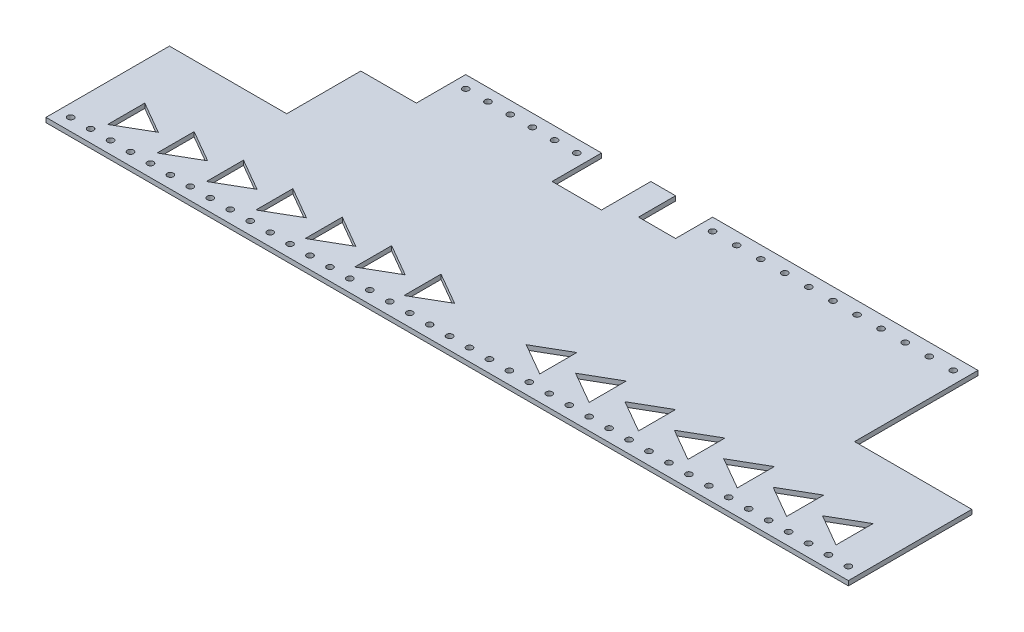
SolidWorks part; units mm, degrees
note: The reader was unsure of these and kept them because the rebuilt part matched: thickness of "Base-Flange1", "Sheet-Metal1", "Sheet-Metal2", "Sheet-Metal3", "Sheet-Metal4", "Sheet-Metal5", "Sheet-Metal6", "Sheet-Metal7".
material "6061 Alloy"
ref_plane "Front Plane" through (0, 0, 0) normal (0, 0, 1) x (1, 0, 0)
ref_plane "Top Plane" through (0, 0, 0) normal (0, 1, 0) x (1, 0, 0)
ref_plane "Right Plane" through (0, 0, 0) normal (1, 0, 0) x (0, 0, -1)
sketch "Sketch1" plane through (0, 0, 0) normal (0, 1, 0) x (1, 0, 0)
  line L1 (412.75, 127) -> (-412.75, 127)
  line L2 (412.75, 127) -> (412.75, -127)
  line L3 (412.75, -127) -> (-412.75, -127)
  line L4 (-412.75, 127) -> (-412.75, -127)
  line L5 (412.75, 127) -> (-412.75, -127) construction
  line L6 (412.75, -127) -> (-412.75, 127) construction
  point P0 (0, 0)
  dimension "D1" = 254
  dimension "D2" = 825.5
base flange "Base-Flange1" sketch "Sketch1" thickness 4.7625 reverse thickness direction no parameters "D1"=3.175
sketch "Sketch6" plane through (0, 0, 0) normal (0, 1, 0) x (1, 0, 0)
  line L0 (412.75, 127) -> (-412.75, 127) construction
  line L1 (-19.05, 165.1) -> (19.05, 165.1)
  line L2 (-19.05, 165.1) -> (-19.05, 88.9)
  line L3 (-19.05, 88.9) -> (19.05, 88.9)
  line L4 (19.05, 165.1) -> (19.05, 88.9)
  line L5 (-19.05, 165.1) -> (19.05, 88.9) construction
  line L6 (-19.05, 88.9) -> (19.05, 165.1) construction
  line L7 (-412.75, 127) -> (-412.75, -127) construction
  line L8 (-533.4, 101.6) -> (-292.1, 101.6)
  line L9 (-533.4, 101.6) -> (-533.4, 0)
  line L10 (-533.4, 0) -> (-292.1, 0)
  line L11 (-292.1, 101.6) -> (-292.1, 0)
  line L12 (-533.4, 101.6) -> (-292.1, 0) construction
  line L13 (-533.4, 0) -> (-292.1, 101.6) construction
  line L14 (412.75, -127) -> (412.75, 127) construction
  line L15 (533.4, 0) -> (292.1, 0)
  line L16 (533.4, 0) -> (533.4, 101.6)
  line L17 (533.4, 101.6) -> (292.1, 101.6)
  line L18 (292.1, 0) -> (292.1, 101.6)
  line L19 (533.4, 0) -> (292.1, 101.6) construction
  line L20 (533.4, 101.6) -> (292.1, 0) construction
  line L22 (-44.45, 76.2) -> (-95.25, 76.2)
  line L23 (-44.45, 76.2) -> (-44.45, 177.8)
  line L24 (-44.45, 177.8) -> (-95.25, 177.8)
  line L25 (-95.25, 76.2) -> (-95.25, 177.8)
  line L26 (-44.45, 76.2) -> (-95.25, 177.8) construction
  line L27 (-44.45, 177.8) -> (-95.25, 76.2) construction
  point P0 (0, 127)
  point P7 (-412.75, 50.8)
  point P14 (412.75, 50.8)
  point P21 (-69.85, 127)
  dimension "D1" = 38.1
  dimension "D2" = 76.2
  dimension "D3" = 241.3
  dimension "D4" = 101.6
  dimension "D5" = 25.4
  dimension "D6" = 241.3
  dimension "D7" = 101.6
  dimension "D8" = 25.4
  dimension "D9" = 50.8
  dimension "D10" = 101.6
  dimension "D11" = 25.4
extrude "Cut-Extrude1" cut sketch "Sketch6" against normal through all normal cut yes
sketch "Sketch7" plane through (0, 0, 0) normal (0, 1, 0) x (1, 0, 0)
  line L1 (-412.75, 127) -> (-234.95, 127)
  line L2 (-412.75, 127) -> (-412.75, 76.2)
  line L3 (-412.75, 76.2) -> (-234.95, 76.2)
  line L4 (-234.95, 127) -> (-234.95, 76.2)
  line L5 (412.75, 127) -> (292.1, 127)
  line L6 (412.75, 127) -> (412.75, 101.6)
  line L7 (412.75, 101.6) -> (292.1, 101.6)
  line L8 (292.1, 127) -> (292.1, 101.6)
  dimension "D1" = 50.8
  dimension "D2" = 177.8
extrude "Cut-Extrude2" cut sketch "Sketch7" against normal through all normal cut yes
sketch "Sketch8" plane through (0, 0, 0) normal (0, 1, 0) x (1, 0, 0)
  line L0 (412.75, -127) -> (412.75, 0) construction
  line L1 (341.6544, -82.55) -> (374.65, -101.6)
  line L2 (374.65, -101.6) -> (374.65, -63.5)
  line L3 (374.65, -63.5) -> (341.6544, -82.55)
  line L4 (323.85, -101.6) -> (323.85, -63.5)
  line L5 (323.85, -63.5) -> (290.8544, -82.55)
  line L6 (290.8544, -82.55) -> (323.85, -101.6)
  line L7 (273.05, -101.6) -> (273.05, -63.5)
  line L8 (273.05, -63.5) -> (240.0544, -82.55)
  line L9 (240.0544, -82.55) -> (273.05, -101.6)
  line L10 (222.25, -101.6) -> (222.25, -63.5)
  line L11 (222.25, -63.5) -> (189.2544, -82.55)
  line L12 (189.2544, -82.55) -> (222.25, -101.6)
  line L13 (171.45, -101.6) -> (171.45, -63.5)
  line L14 (171.45, -63.5) -> (138.4544, -82.55)
  line L15 (138.4544, -82.55) -> (171.45, -101.6)
  line L16 (120.65, -101.6) -> (120.65, -63.5)
  line L17 (120.65, -63.5) -> (87.6544, -82.55)
  line L18 (87.6544, -82.55) -> (120.65, -101.6)
  line L19 (69.85, -101.6) -> (69.85, -63.5)
  line L20 (69.85, -63.5) -> (36.8544, -82.55)
  line L21 (36.8544, -82.55) -> (69.85, -101.6)
  line L22 (0, 0) -> (0, -95.9685) construction
  line L23 (-36.8544, -82.55) -> (-69.85, -101.6)
  line L24 (-69.85, -63.5) -> (-36.8544, -82.55)
  line L25 (-69.85, -101.6) -> (-69.85, -63.5)
  line L26 (-87.6544, -82.55) -> (-120.65, -101.6)
  line L27 (-120.65, -63.5) -> (-87.6544, -82.55)
  line L28 (-120.65, -101.6) -> (-120.65, -63.5)
  line L29 (-138.4544, -82.55) -> (-171.45, -101.6)
  line L30 (-171.45, -63.5) -> (-138.4544, -82.55)
  line L31 (-171.45, -101.6) -> (-171.45, -63.5)
  line L32 (-189.2544, -82.55) -> (-222.25, -101.6)
  line L33 (-222.25, -63.5) -> (-189.2544, -82.55)
  line L34 (-222.25, -101.6) -> (-222.25, -63.5)
  line L35 (-240.0544, -82.55) -> (-273.05, -101.6)
  line L36 (-273.05, -63.5) -> (-240.0544, -82.55)
  line L37 (-273.05, -101.6) -> (-273.05, -63.5)
  line L38 (-290.8544, -82.55) -> (-323.85, -101.6)
  line L39 (-323.85, -63.5) -> (-290.8544, -82.55)
  line L40 (-323.85, -101.6) -> (-323.85, -63.5)
  line L41 (-374.65, -63.5) -> (-341.6544, -82.55)
  line L42 (-374.65, -101.6) -> (-374.65, -63.5)
  line L43 (-341.6544, -82.55) -> (-374.65, -101.6)
  line L46 (-412.75, -127) -> (412.75, -127) construction
  line L47 (19.05, -101.6) -> (19.05, -63.5) [skipped]
  line L48 (-13.9456, -82.55) -> (19.05, -101.6) [skipped]
  line L49 (19.05, -63.5) -> (-13.9456, -82.55) [skipped]
  line L50 (-31.75, -63.5) -> (-64.7456, -82.55) [skipped]
  line L51 (-31.75, -101.6) -> (-31.75, -63.5) [skipped]
  line L52 (-64.7456, -82.55) -> (-31.75, -101.6) [skipped]
  line L53 (-82.55, -101.6) -> (-82.55, -63.5) [skipped]
  line L54 (-82.55, -63.5) -> (-115.5456, -82.55) [skipped]
  line L55 (-115.5456, -82.55) -> (-82.55, -101.6) [skipped]
  line L56 (-133.35, -101.6) -> (-133.35, -63.5) [skipped]
  line L57 (-133.35, -63.5) -> (-166.3456, -82.55) [skipped]
  line L58 (-166.3456, -82.55) -> (-133.35, -101.6) [skipped]
  line L59 (-184.15, -101.6) -> (-184.15, -63.5) [skipped]
  line L60 (-184.15, -63.5) -> (-217.1456, -82.55) [skipped]
  line L61 (-217.1456, -82.55) -> (-184.15, -101.6) [skipped]
  line L62 (-234.95, -101.6) -> (-234.95, -63.5) [skipped]
  line L63 (-234.95, -63.5) -> (-267.9456, -82.55) [skipped]
  line L64 (-267.9456, -82.55) -> (-234.95, -101.6) [skipped]
  line L65 (-285.75, -101.6) -> (-285.75, -63.5) [skipped]
  line L66 (-285.75, -63.5) -> (-318.7456, -82.55) [skipped]
  line L67 (-318.7456, -82.55) -> (-285.75, -101.6) [skipped]
  line L68 (-336.55, -101.6) -> (-336.55, -63.5) [skipped]
  line L69 (-336.55, -63.5) -> (-369.5456, -82.55) [skipped]
  line L70 (-369.5456, -82.55) -> (-336.55, -101.6) [skipped]
  circle A0 centre (363.6515, -82.55) radius 10.9985 construction
  circle A1 centre (-363.6515, -82.55) radius 10.9985 construction
  dimension "D1" = 38.1
  dimension "D2" = 38.1
  dimension "D4" = 25.4
  dimension "D3" = 15
extrude "Cut-Extrude3" cut sketch "Sketch8" against normal through all normal cut yes
sketch "Sketch9" plane through (0, 0, 0) normal (0, 1, 0) x (1, 0, 0)
  line L0 (292.1, 127) -> (292.1, 0) construction
  line L1 (292.1, 127) -> (19.05, 127) construction
  line L2 (19.05, 88.9) -> (19.05, 127) construction
  circle A0 centre (279.4, 114.3) radius 3.175
  circle A1 centre (254.635, 114.3) radius 3.175
  circle A2 centre (229.87, 114.3) radius 3.175
  circle A3 centre (205.105, 114.3) radius 3.175
  circle A4 centre (180.34, 114.3) radius 3.175
  circle A5 centre (155.575, 114.3) radius 3.175
  circle A6 centre (130.81, 114.3) radius 3.175
  circle A7 centre (106.045, 114.3) radius 3.175
  circle A8 centre (81.28, 114.3) radius 3.175
  circle A9 centre (56.515, 114.3) radius 3.175
  circle A10 centre (31.75, 114.3) radius 3.175
  dimension "D1" = 6.35
  dimension "D2" = 12.7
  dimension "D3" = 12.7
  dimension "D5" = 12.7
  dimension "D4" = 11
extrude "Cut-Extrude4" cut sketch "Sketch9" against normal blind 7.62 normal cut yes
sketch "Sketch10" plane through (0, 0, 0) normal (0, 1, 0) x (1, 0, 0)
  line L0 (412.75, -127) -> (412.75, 0) construction
  line L1 (-412.75, -127) -> (412.75, -127) construction
  line L2 (-412.75, 0) -> (-412.75, -127) construction
  circle A0 centre (400.05, -114.3) radius 3.175
  circle A1 centre (379.5346, -114.3) radius 3.175
  circle A2 centre (359.0192, -114.3) radius 3.175
  circle A3 centre (338.5038, -114.3) radius 3.175
  circle A4 centre (317.9885, -114.3) radius 3.175
  circle A5 centre (297.4731, -114.3) radius 3.175
  circle A6 centre (276.9577, -114.3) radius 3.175
  circle A7 centre (256.4423, -114.3) radius 3.175
  circle A8 centre (235.9269, -114.3) radius 3.175
  circle A9 centre (215.4115, -114.3) radius 3.175
  circle A10 centre (194.8962, -114.3) radius 3.175
  circle A11 centre (174.3808, -114.3) radius 3.175
  circle A12 centre (153.8654, -114.3) radius 3.175
  circle A13 centre (133.35, -114.3) radius 3.175
  circle A14 centre (112.8346, -114.3) radius 3.175
  circle A15 centre (92.3192, -114.3) radius 3.175
  circle A16 centre (71.8038, -114.3) radius 3.175
  circle A17 centre (51.2885, -114.3) radius 3.175
  circle A18 centre (30.7731, -114.3) radius 3.175
  circle A19 centre (10.2577, -114.3) radius 3.175
  circle A20 centre (-10.2577, -114.3) radius 3.175
  circle A21 centre (-30.7731, -114.3) radius 3.175
  circle A22 centre (-51.2885, -114.3) radius 3.175
  circle A23 centre (-71.8038, -114.3) radius 3.175
  circle A24 centre (-92.3192, -114.3) radius 3.175
  circle A25 centre (-112.8346, -114.3) radius 3.175
  circle A26 centre (-133.35, -114.3) radius 3.175
  circle A27 centre (-153.8654, -114.3) radius 3.175
  circle A28 centre (-174.3808, -114.3) radius 3.175
  circle A29 centre (-194.8962, -114.3) radius 3.175
  circle A30 centre (-215.4115, -114.3) radius 3.175
  circle A31 centre (-235.9269, -114.3) radius 3.175
  circle A32 centre (-256.4423, -114.3) radius 3.175
  circle A33 centre (-276.9577, -114.3) radius 3.175
  circle A34 centre (-297.4731, -114.3) radius 3.175
  circle A35 centre (-317.9885, -114.3) radius 3.175
  circle A36 centre (-338.5038, -114.3) radius 3.175
  circle A37 centre (-359.0192, -114.3) radius 3.175
  circle A38 centre (-379.5346, -114.3) radius 3.175
  circle A39 centre (-400.05, -114.3) radius 3.175
  dimension "D1" = 6.35
  dimension "D2" = 12.7
  dimension "D3" = 12.7
  dimension "D5" = 12.7
  dimension "D4" = 40
extrude "Cut-Extrude5" cut sketch "Sketch10" against normal blind 7.62 normal cut yes
sketch "Sketch11" plane through (0, 0, 0) normal (0, 1, 0) x (1, 0, 0)
  line L0 (-95.25, 76.2) -> (-95.25, 127) construction
  line L1 (-95.25, 127) -> (-234.95, 127) construction
  line L2 (-234.95, 76.2) -> (-234.95, 127) construction
  circle A0 centre (-107.95, 114.3) radius 3.175
  circle A1 centre (-130.81, 114.3) radius 3.175
  circle A2 centre (-153.67, 114.3) radius 3.175
  circle A3 centre (-176.53, 114.3) radius 3.175
  circle A4 centre (-199.39, 114.3) radius 3.175
  circle A5 centre (-222.25, 114.3) radius 3.175
  dimension "D1" = 6.35
  dimension "D2" = 12.7
  dimension "D3" = 12.7
  dimension "D5" = 12.7
  dimension "D4" = 6
extrude "Cut-Extrude6" cut sketch "Sketch11" against normal blind 7.62 normal cut yes
sketch "Bend-Lines1" plane through (0, 0, 0) normal (0, 1, 0) x (1, 0, 0)
sketch "Bounding-Box1" plane through (0, 0, 0) normal (0, 1, 0) x (1, 0, 0)
sheet metal parameters "Sheet-Metal1" thickness 4.7625 parameters "D1"=3.175, "D7"=6.35
flat pattern "Flat-Pattern1" [suppressed]
sketch "Bend-Lines2" plane through (0, 0, 0) normal (0, 1, 0) x (1, 0, 0)
sketch "Bounding-Box2" [suppressed] plane through (0, 0, 0) normal (0, 1, 0) x (1, 0, 0)
sheet metal parameters "Sheet-Metal2" thickness 4.7625 parameters "D1"=3.175, "D7"=6.35
flat pattern "Flat-Pattern1"
sketch "Bend-Lines2" plane through (0, 0, 0) normal (0, 1, 0) x (1, 0, 0)
sketch "Bounding-Box2" [suppressed] plane through (0, 0, 0) normal (0, 1, 0) x (1, 0, 0)
sheet metal parameters "Sheet-Metal3" thickness 4.7625 parameters "D1"=3.175, "D7"=6.35
flat pattern "Flat-Pattern1"
sketch "Bend-Lines2" plane through (0, 0, 0) normal (0, 1, 0) x (1, 0, 0)
sketch "Bounding-Box2" [suppressed] plane through (0, 0, 0) normal (0, 1, 0) x (1, 0, 0)
sheet metal parameters "Sheet-Metal4" thickness 4.7625 parameters "D1"=3.175, "D7"=6.35
flat pattern "Flat-Pattern1"
sketch "Bend-Lines2" plane through (0, 0, 0) normal (0, 1, 0) x (1, 0, 0)
sketch "Bounding-Box2" [suppressed] plane through (0, 0, 0) normal (0, 1, 0) x (1, 0, 0)
sheet metal parameters "Sheet-Metal5" thickness 4.7625 parameters "D1"=3.175, "D7"=6.35
flat pattern "Flat-Pattern1"
sketch "Bend-Lines2" plane through (0, 0, 0) normal (0, 1, 0) x (1, 0, 0)
sketch "Bounding-Box2" [suppressed] plane through (0, 0, 0) normal (0, 1, 0) x (1, 0, 0)
sheet metal parameters "Sheet-Metal6" thickness 4.7625 parameters "D1"=3.175, "D7"=6.35
flat pattern "Flat-Pattern1"
sketch "Bend-Lines2" plane through (0, 0, 0) normal (0, 1, 0) x (1, 0, 0)
sketch "Bounding-Box2" [suppressed] plane through (0, 0, 0) normal (0, 1, 0) x (1, 0, 0)
sheet metal parameters "Sheet-Metal7" thickness 4.7625 parameters "D1"=3.175, "D7"=6.35
flat pattern "Flat-Pattern1"
sketch "Bend-Lines2" plane through (0, 0, 0) normal (0, 1, 0) x (1, 0, 0)
sketch "Bounding-Box2" [suppressed] plane through (0, 0, 0) normal (0, 1, 0) x (1, 0, 0)
